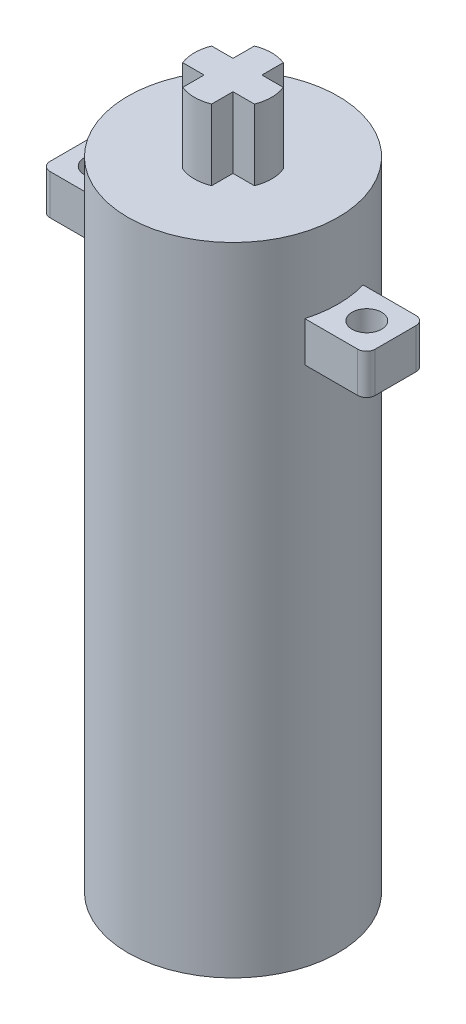
SolidWorks part; units mm, degrees
material "Plain Carbon Steel"
ref_plane "Front Plane" through (0, 0, 0) normal (0, 0, 1) x (1, 0, 0)
ref_plane "Top Plane" through (0, 0, 0) normal (0, 1, 0) x (1, 0, 0)
ref_plane "Right Plane" through (0, 0, 0) normal (1, 0, 0) x (0, 0, -1)
sketch "VigorSketch" plane through (0, 0, 0) normal (0, 1, 0) x (1, 0, 0)
  line L0 (0, -1.665) -> (0, 1.665)
  line L1 (-8.785, 1.665) -> (8.785, 1.665)
  line L2 (-9.285, 1.165) -> (-9.285, -1.165)
  line L3 (-8.785, -1.665) -> (8.785, -1.665)
  line L4 (9.285, 1.165) -> (9.285, -1.165)
  line L5 (2.0449, 0.8249) -> (0.8249, 0.8249)
  line L6 (0.8249, 0.8249) -> (0.8249, 2.0449)
  line L7 (-0.8249, 2.0449) -> (-0.8249, 0.8249)
  line L8 (-0.8249, 0.8249) -> (-2.0449, 0.8249)
  line L9 (-2.0449, -0.8249) -> (-0.8249, -0.8249)
  line L10 (-0.8249, -0.8249) -> (-0.8249, -2.0449)
  line L11 (2.0449, -0.8249) -> (0.8249, -0.8249)
  line L12 (0.8249, -0.8249) -> (0.8249, -2.0449)
  circle A0 centre (0, 0) radius 6
  arc A1 (-8.785, -1.665) -> (-9.285, -1.165) centre (-8.785, -1.165) cw
  arc A2 (9.285, -1.165) -> (8.785, -1.665) centre (8.785, -1.165) cw
  arc A3 (9.285, 1.165) -> (8.785, 1.665) centre (8.785, 1.165) ccw
  arc A4 (-8.785, 1.665) -> (-9.285, 1.165) centre (-8.785, 1.165) ccw
  circle A5 centre (7.6425, 0) radius 0.845
  circle A6 centre (-7.6425, 0) radius 0.845
  circle A7 centre (0, 0) radius 2.205
  point P7 (-9.285, 0)
  point P8 (9.285, 0)
  point P9 (0, 1.665)
  point P10 (0, -1.665)
  point P15 (9.285, -1.665)
  point P18 (9.285, 1.665)
  point P21 (-9.285, 1.665)
  dimension "D1" = 12
  dimension "D4" = 0.5
  dimension "D5" = 1.69
  dimension "D8" = 4.41
  dimension "D2" = 18.57
  dimension "D3" = 3.33
  dimension "D6" = 1.6425
  dimension "D7" = 1.665
  dimension "D9" = 1.22
extrude "VigorFlange" add sketch "VigorSketch" along normal blind 2.29 contours L1 A4 L2 A1 L3 A0 A6 | L1 A0 L3 L0 | L3 A0 L1 L0 | L4 A3 L1 A0 L3 A2 A5 region at (-3.9418, 0, 0) region at (3.9418, 0, 0) region at (-7.2747, 0, 1.6165) region at (5.9888, 0, 0.8476)
extrude "VigorAxle" add sketch "Sketch1<7>" along normal blind 10.62 contours L11 A7 L5 L6 L1 L0 L3 L12 | L8 A7 L9 L10 L3 L0 L1 L7 | L6 A7 L7 L1 | L10 A7 L12 L3 region at (-0.8902, 0, 0) region at (0, 0, 1.911) region at (0.8902, 0, 0) region at (0, 0, -1.911)
sketch "Sketch1<7>" plane through (0, 0, 0) normal (0, 1, 0) x (1, 0, 0) same geometry as "VigorSketch"
extrude "VigorBody" add sketch "VigorSketch<8>" along normal blind 6.58 and the other way blind 29.7899 contours A7 L1 A0 | A7 L3 A0 | L9 A7 L3 L10 | L1 A7 L8 L7 | L5 A7 L1 L6 | L3 A7 L11 L12 | L12 A7 L3 | L1 A7 L6 | L7 A7 L1 | L3 A7 L10 | A7 L1 A0 L3 | A7 L3 A0 L1 | L8 A7 L9 L10 L3 L0 L1 L7 | L11 A7 L5 L6 L1 L0 L3 L12 | L6 A7 L7 L1 | L10 A7 L12 L3 region at (-0.8902, 0, 0) region at (0, 0, 1.911) region at (0.8902, 0, 0) region at (0, 0, -1.911) region at (-1.044, 0, 1.7998) region at (-1.3254, 0, 1.2025) region at (1.3254, 0, 1.2025) region at (1.044, 0, 1.7998) region at (-1.3254, 0, -1.2025) region at (-1.044, 0, -1.7998) region at (1.044, 0, -1.7998) region at (1.3254, 0, -1.2025) region at (0, 0, 3.5146) region at (-3.9418, 0, 0) region at (3.9418, 0, 0) region at (0, 0, -3.5146)
sketch "VigorSketch<8>" plane through (0, 0, 0) normal (0, 1, 0) x (1, 0, 0) same geometry as "VigorSketch"
equation "\"vigorwidth\"= 0.472441in"
equation "\"D1@VigorSketch\"=\"vigorwidth\""
equation "\"vigorflangewidth\"= 0.731102in"
equation "\"D2@VigorSketch\"=\"vigorflangewidth\""
equation "\"vigorflangelength\"= 0.131102in"
equation "\"D3@VigorSketch\"=\"vigorflangelength\""
equation "\"vigorscrewsize\"= 0.066535in"
equation "\"D5@VigorSketch\"=\"vigorscrewsize\""
equation "\"vigorholeoffsetwid\"= 0.0646653in"
equation "\"D6@VigorSketch\"=\"vigorholeoffsetwid\""
equation "\"vigorholeoffsetlen\"= 0.065551in"
equation "\"D7@VigorSketch\"= \"vigorholeoffsetlen\""
equation "\"vigorflangedepth\"= 0.0901575in"
equation "\"vigordiscdepth\"= 0.0492126in"
equation "\"vigormotordepth\"= 1.12362in"
equation "\"vigortipdepth\"= 0.259055in"
equation "\"vigoraxlewidth\"= 0.173622in"
equation "\"D8@VigorSketch\"=\"vigoraxlewidth\""
equation "\"vigorcutlen\"= 0.0480315in"
equation "\"D9@VigorSketch\"=\"vigorcutlen\""
equation "\"vigoraxledepth\"= 0.159055in"
equation "\"D1@VigorBody\"=\"vigortipdepth\""
equation "\"D2@VigorBody\"=\"vigordiscdepth\"+\"vigormotordepth\""
equation "\"D1@VigorFlange\"=\"vigorflangedepth\""
equation "\"D1@VigorAxle\"=\"vigortipdepth\"+\"vigoraxledepth\""
